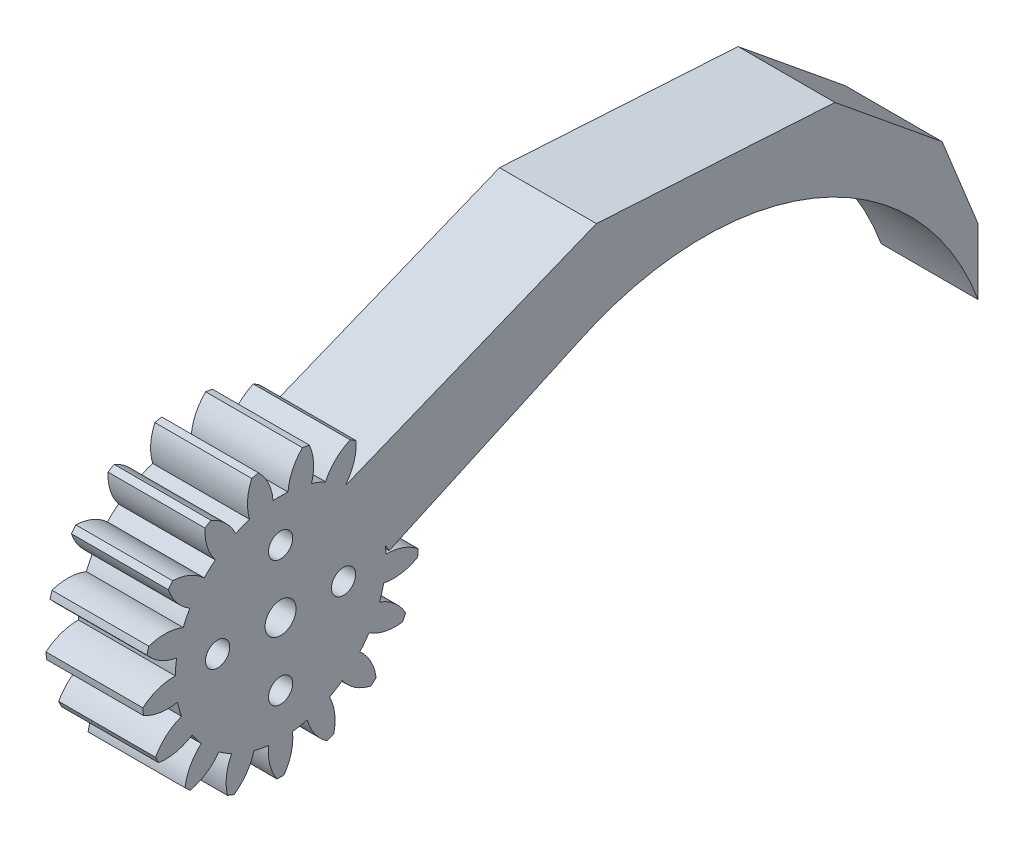
SolidWorks part; units mm, degrees
ref_plane "前视基准面" through (0, 0, 0) normal (0, 0, 1) x (1, 0, 0)
ref_plane "上视基准面" through (0, 0, 0) normal (0, 1, 0) x (1, 0, 0)
ref_plane "右视基准面" through (0, 0, 0) normal (1, 0, 0) x (0, 0, -1)
other "Configuration Table"
sketch "草图1" plane through (0, 0, 0) normal (1, 0, 0) x (0, 0, -1)
  circle A0 centre (-0.6201, 7.5553) radius 12.75 construction
  arc A1 (-14.4217, 11.1021) -> (-11.3496, 9.3222) centre (-10.4888, 14.3491) ccw
  arc A2 (-11.3496, 9.3222) -> (-11.4916, 7.7901) centre (-0.6201, 7.5553) ccw
  arc A3 (-11.4916, 7.7901) -> (-14.8384, 6.605) centre (-11.5692, 2.6907) ccw
  arc A4 (-14.8384, 6.605) -> (-14.7709, 5.8769) centre (-0.6201, 7.5553) ccw
  arc A5 (-14.7709, 5.8769) -> (-11.2633, 5.327) centre (-12.2766, 10.3253) ccw
  arc A6 (-11.2633, 5.327) -> (-10.8423, 3.847) centre (-0.6201, 7.5553) ccw
  arc A7 (-10.8423, 3.847) -> (-13.535, 1.5329) centre (-9.0725, -0.9361) ccw
  arc A8 (-13.535, 1.5329) -> (-13.209, 0.8784) centre (-0.6201, 7.5553) ccw
  arc A9 (-13.209, 0.8784) -> (-9.7397, 1.6327) centre (-12.4901, 5.9274) ccw
  arc A10 (-9.7397, 1.6327) -> (-8.8124, 0.4047) centre (-0.6201, 7.5553) ccw
  arc A11 (-8.8124, 0.4047) -> (-10.4873, -2.7258) centre (-5.4342, -3.416) ccw
  arc A12 (-10.4873, -2.7258) -> (-9.9469, -3.2184) centre (-0.6201, 7.5553) ccw
  arc A13 (-9.9469, -3.2184) -> (-6.9843, -1.2617) centre (-11.1005, 1.7494) ccw
  arc A14 (-6.9843, -1.2617) -> (-5.6761, -2.0718) centre (-0.6201, 7.5553) ccw
  arc A15 (-5.6761, -2.0718) -> (-6.1071, -5.5959) centre (-1.1459, -4.4142) ccw
  arc A16 (-6.1071, -5.5959) -> (-5.4252, -5.8601) centre (-0.6201, 7.5553) ccw
  arc A17 (-5.4252, -5.8601) -> (-3.3695, -2.9654) centre (-8.2954, -1.6444) ccw
  arc A18 (-3.3695, -2.9654) -> (-1.857, -3.2481) centre (-0.6201, 7.5553) ccw
  arc A19 (-1.857, -3.2481) -> (-0.9857, -6.69) centre (3.2135, -3.7958) ccw
  arc A20 (-0.9857, -6.69) -> (-0.2545, -6.69) centre (-0.6201, 7.5553) ccw
  arc A21 (-0.2545, -6.69) -> (0.6167, -3.2481) centre (-4.4538, -3.7958) ccw
  arc A22 (0.6167, -3.2481) -> (2.1292, -2.9654) centre (-0.6201, 7.5553) ccw
  arc A23 (2.1292, -2.9654) -> (4.1849, -5.8601) centre (7.0552, -1.6444) ccw
  arc A24 (4.1849, -5.8601) -> (4.8668, -5.5959) centre (-0.6201, 7.5553) ccw
  arc A25 (4.8668, -5.5959) -> (4.4358, -2.0718) centre (-0.0944, -4.4142) ccw
  arc A26 (4.4358, -2.0718) -> (5.7441, -1.2617) centre (-0.6201, 7.5553) ccw
  arc A27 (5.7441, -1.2617) -> (8.7067, -3.2184) centre (9.8602, 1.7494) ccw
  arc A28 (8.7067, -3.2184) -> (9.2471, -2.7258) centre (-0.6201, 7.5553) ccw
  arc A29 (9.2471, -2.7258) -> (7.5721, 0.4047) centre (4.194, -3.416) ccw
  arc A30 (7.5721, 0.4047) -> (8.4994, 1.6327) centre (-0.6201, 7.5553) ccw
  arc A31 (8.4994, 1.6327) -> (11.9688, 0.8784) centre (11.2498, 5.9274) ccw
  arc A32 (11.9688, 0.8784) -> (12.2947, 1.5329) centre (-0.6201, 7.5553) ccw
  arc A33 (12.2947, 1.5329) -> (9.602, 3.847) centre (7.8322, -0.9361) ccw
  arc A34 (9.602, 3.847) -> (10.0231, 5.327) centre (-0.6201, 7.5553) ccw
  arc A35 (10.0231, 5.327) -> (13.5307, 5.8769) centre (11.0364, 10.3253) ccw
  arc A36 (13.5307, 5.8769) -> (13.5982, 6.605) centre (-0.6201, 7.5553) ccw
  arc A37 (13.5982, 6.605) -> (10.2513, 7.7901) centre (10.3289, 2.6907) ccw
  arc A38 (10.2513, 7.7901) -> (10.1094, 9.3222) centre (-0.6201, 7.5553) ccw
  arc A39 (10.1094, 9.3222) -> (13.1814, 11.1021) centre (9.2486, 14.3491) ccw
  arc A40 (13.1814, 11.1021) -> (12.9813, 11.8054) centre (-0.6201, 7.5553) ccw
  arc A41 (12.9813, 11.8054) -> (9.4324, 11.7014) centre (11.3469, 6.9744) ccw
  arc A42 (9.4324, 11.7014) -> (8.7466, 13.0788) centre (-0.6201, 7.5553) ccw
  arc A43 (8.7466, 13.0788) -> (10.9682, 15.8483) centre (6.128, 17.4553) ccw
  arc A44 (10.9682, 15.8483) -> (10.5275, 16.4318) centre (-0.6201, 7.5553) ccw
  arc A45 (10.5275, 16.4318) -> (7.2558, 15.0529) centre (10.7486, 11.3366) ccw
  arc A46 (7.2558, 15.0529) -> (6.1187, 16.0895) centre (-0.6201, 7.5553) ccw
  arc A47 (6.1187, 16.0895) -> (7.1899, 19.4745) centre (2.0961, 19.2245) ccw
  arc A48 (7.1899, 19.4745) -> (6.5682, 19.8594) centre (-0.6201, 7.5553) ccw
  arc A49 (6.5682, 19.8594) -> (4.0156, 17.3917) centre (8.615, 15.1881) ccw
  arc A50 (4.0156, 17.3917) -> (2.5808, 17.9475) centre (-0.6201, 7.5553) ccw
  arc A51 (2.5808, 17.9475) -> (2.3568, 21.4909) centre (-2.3027, 19.4177) ccw
  arc A52 (2.3568, 21.4909) -> (1.6381, 21.6253) centre (-0.6201, 7.5553) ccw
  arc A53 (1.6381, 21.6253) -> (0.1492, 18.4021) centre (5.234, 18.0088) ccw
  arc A54 (0.1492, 18.4021) -> (-1.3895, 18.4021) centre (-0.6201, 7.5553) ccw
  arc A55 (-1.3895, 18.4021) -> (-2.8783, 21.6253) centre (-6.4743, 18.0088) ccw
  arc A56 (-2.8783, 21.6253) -> (-3.5971, 21.4909) centre (-0.6201, 7.5553) ccw
  arc A57 (-3.5971, 21.4909) -> (-3.821, 17.9475) centre (1.0625, 19.4177) ccw
  arc A58 (-3.821, 17.9475) -> (-5.2558, 17.3917) centre (-0.6201, 7.5553) ccw
  arc A59 (-5.2558, 17.3917) -> (-7.8085, 19.8594) centre (-9.8552, 15.1881) ccw
  arc A60 (-7.8085, 19.8594) -> (-8.4302, 19.4745) centre (-0.6201, 7.5553) ccw
  arc A61 (-8.4302, 19.4745) -> (-7.359, 16.0895) centre (-3.3363, 19.2245) ccw
  arc A62 (-7.359, 16.0895) -> (-8.4961, 15.0529) centre (-0.6201, 7.5553) ccw
  arc A63 (-8.4961, 15.0529) -> (-11.7678, 16.4318) centre (-11.9889, 11.3366) ccw
  arc A64 (-11.7678, 16.4318) -> (-12.2085, 15.8483) centre (-0.6201, 7.5553) ccw
  arc A65 (-12.2085, 15.8483) -> (-9.9868, 13.0788) centre (-7.3683, 17.4553) ccw
  arc A66 (-9.9868, 13.0788) -> (-10.6727, 11.7014) centre (-0.6201, 7.5553) ccw
  arc A67 (-10.6727, 11.7014) -> (-14.2216, 11.8054) centre (-12.5871, 6.9744) ccw
  arc A68 (-14.2216, 11.8054) -> (-14.4217, 11.1021) centre (-0.6201, 7.5553) ccw
extrude "凸台-拉伸1" add sketch "草图1" along normal blind 10
sketch "草图2" plane through (10, 0, 0) normal (1, 0, 0) x (0, 0, -1)
  circle A0 centre (-0.6201, 7.5553) radius 1.7242
  dimension "D1" = 3.4484
extrude "切除-拉伸1" cut sketch "草图2" against normal blind 10
sketch "草图5" [suppressed] plane through (10, 0, 0) normal (1, 0, 0) x (0, 0, -1)
  circle A0 centre (-0.6201, 7.5553) radius 12.75 construction
sketch "草图7" [suppressed] plane through (10, 0, 0) normal (1, 0, 0) x (0, 0, -1)
  line L0 (-38.8515, 60.5868) -> (-49.9964, 49.4419)
  line L1 (-13.0532, 39.26) -> (-111.5146, 39.26) construction
  line L2 (-50.689, 49.4419) -> (-49.9964, 49.4419)
  line L3 (9.7389, 56.4365) -> (20.6157, 52.1796)
  line L4 (-50.689, 49.4419) -> (-90.8971, 49.4419)
  line L5 (-90.8971, 49.4419) -> (-90.8971, 62.9419)
  line L6 (-90.8971, 62.9419) -> (-53.9638, 65.5245)
  line L7 (7.5721, 0.4047) -> (7.5721, 11.8054)
  line L8 (7.5721, 11.8054) -> (44.482, 14.3864)
  line L9 (7.5721, 0.4047) -> (47.7721, 0.4047)
  line L10 (47.7721, 0.4047) -> (58.7323, 11.3649)
  line L11 (107.2323, 7.4047) -> (118.7323, 3.1047)
  arc A0 (-38.8515, 60.5868) -> (9.7389, 56.4365) centre (-17.9459, 18.8274) cw
  arc A1 (-53.9638, 65.5245) -> (20.6157, 52.1796) centre (-22.4221, 26.7287) cw
  arc A2 (58.7323, 11.3649) -> (107.2323, 7.4047) centre (79.7383, -30.3441) cw
  arc A3 (44.482, 14.3864) -> (118.7323, 3.1047) centre (76.6479, -23.8935) cw
  dimension "D5" = 50
  dimension "D12" = 46.7
  dimension "D13" = 46.7
  dimension "D14" = 50
  dimension "D16" = 7
  dimension "D1" = 45
  dimension "D2" = 13.5
  dimension "D3" = 94
  dimension "D4" = 94
  dimension "D6" = 40.2
  dimension "D7" = 37
  dimension "D8" = 135
  dimension "D9" = 15.5
  dimension "D10" = 48.5904
  dimension "D11" = 48.5
  dimension "D15" = 60
  dimension "D17" = 2.7
extrude "凸台-拉伸4" add sketch "草图1<2>" along normal blind 10
sketch "草图1<2>" plane through (0, 0, 0) normal (1, 0, 0) x (0, 0, -1) same geometry as "草图1"
sketch "草图9" plane through (10, 0, 0) normal (1, 0, 0) x (0, 0, -1)
  circle A0 centre (-0.6201, 7.5553) radius 1.6
  dimension "D1" = 3.2
extrude "切除-拉伸2" cut sketch "草图9" against normal blind 10
sketch "草图10" plane through (10, 0, 0) normal (1, 0, 0) x (0, 0, -1)
  circle A0 centre (-0.6201, 7.5553) radius 12.75
  arc A60 (-14.4217, 11.1021) -> (-11.3496, 9.3222) centre (-10.4888, 14.3491) ccw
  arc A61 (-11.3496, 9.3222) -> (-11.4916, 7.7901) centre (-0.6201, 7.5553) ccw
  arc A62 (-11.3496, 9.3222) -> (-11.4916, 7.7901) centre (-0.6201, 7.5553) ccw
  arc A63 (-8.8124, 0.4047) -> (-10.4873, -2.7258) centre (-5.4342, -3.416) ccw
  arc A64 (-10.4873, -2.7258) -> (-9.9469, -3.2184) centre (-0.6201, 7.5553) ccw
  arc A65 (-9.9469, -3.2184) -> (-6.9843, -1.2617) centre (-11.1005, 1.7494) ccw
  arc A66 (-5.6761, -2.0718) -> (-6.1071, -5.5959) centre (-1.1459, -4.4142) ccw
  arc A67 (-6.1071, -5.5959) -> (-5.4252, -5.8601) centre (-0.6201, 7.5553) ccw
  arc A68 (-5.4252, -5.8601) -> (-3.3695, -2.9654) centre (-8.2954, -1.6444) ccw
  arc A69 (-1.857, -3.2481) -> (-0.9857, -6.69) centre (3.2135, -3.7958) ccw
  arc A70 (-0.9857, -6.69) -> (-0.2545, -6.69) centre (-0.6201, 7.5553) ccw
  arc A71 (-0.2545, -6.69) -> (0.6167, -3.2481) centre (-4.4538, -3.7958) ccw
  arc A72 (-11.4916, 7.7901) -> (-14.8384, 6.605) centre (-11.5692, 2.6907) ccw
  arc A73 (0.6167, -3.2481) -> (2.1292, -2.9654) centre (-0.6201, 7.5553) ccw
  arc A74 (2.1292, -2.9654) -> (4.1849, -5.8601) centre (7.0552, -1.6444) ccw
  arc A75 (4.1849, -5.8601) -> (4.8668, -5.5959) centre (-0.6201, 7.5553) ccw
  arc A76 (4.8668, -5.5959) -> (4.4358, -2.0718) centre (-0.0944, -4.4142) ccw
  arc A77 (4.4358, -2.0718) -> (5.7441, -1.2617) centre (-0.6201, 7.5553) ccw
  arc A78 (5.7441, -1.2617) -> (8.7067, -3.2184) centre (9.8602, 1.7494) ccw
  arc A79 (8.7067, -3.2184) -> (9.2471, -2.7258) centre (-0.6201, 7.5553) ccw
  arc A80 (9.2471, -2.7258) -> (7.5721, 0.4047) centre (4.194, -3.416) ccw
  arc A81 (7.5721, 0.4047) -> (8.4994, 1.6327) centre (-0.6201, 7.5553) ccw
  arc A82 (8.4994, 1.6327) -> (11.9688, 0.8784) centre (11.2498, 5.9274) ccw
  arc A83 (11.9688, 0.8784) -> (12.2947, 1.5329) centre (-0.6201, 7.5553) ccw
  arc A84 (12.2947, 1.5329) -> (9.602, 3.847) centre (7.8322, -0.9361) ccw
  arc A85 (9.602, 3.847) -> (10.0231, 5.327) centre (-0.6201, 7.5553) ccw
  arc A86 (10.0231, 5.327) -> (13.5307, 5.8769) centre (11.0364, 10.3253) ccw
  arc A87 (13.5307, 5.8769) -> (13.5982, 6.605) centre (-0.6201, 7.5553) ccw
  arc A88 (13.5982, 6.605) -> (10.2513, 7.7901) centre (10.3289, 2.6907) ccw
  arc A89 (10.2513, 7.7901) -> (10.1094, 9.3222) centre (-0.6201, 7.5553) ccw
  arc A90 (10.1094, 9.3222) -> (13.1814, 11.1021) centre (9.2486, 14.3491) ccw
  arc A91 (13.1814, 11.1021) -> (12.9813, 11.8054) centre (-0.6201, 7.5553) ccw
  arc A92 (12.9813, 11.8054) -> (9.4324, 11.7014) centre (11.3469, 6.9744) ccw
  arc A93 (9.4324, 11.7014) -> (8.7466, 13.0788) centre (-0.6201, 7.5553) ccw
  arc A94 (8.7466, 13.0788) -> (10.9682, 15.8483) centre (6.128, 17.4553) ccw
  arc A95 (10.9682, 15.8483) -> (10.5275, 16.4318) centre (-0.6201, 7.5553) ccw
  arc A96 (10.5275, 16.4318) -> (7.2558, 15.0529) centre (10.7486, 11.3366) ccw
  arc A97 (7.2558, 15.0529) -> (6.1187, 16.0895) centre (-0.6201, 7.5553) ccw
  arc A98 (6.1187, 16.0895) -> (7.1899, 19.4745) centre (2.0961, 19.2245) ccw
  arc A99 (7.1899, 19.4745) -> (6.5682, 19.8594) centre (-0.6201, 7.5553) ccw
  arc A100 (6.5682, 19.8594) -> (4.0156, 17.3917) centre (8.615, 15.1881) ccw
  arc A101 (4.0156, 17.3917) -> (2.5808, 17.9475) centre (-0.6201, 7.5553) ccw
  arc A102 (2.5808, 17.9475) -> (2.3568, 21.4909) centre (-2.3027, 19.4177) ccw
  arc A103 (2.3568, 21.4909) -> (1.6381, 21.6253) centre (-0.6201, 7.5553) ccw
  arc A104 (1.6381, 21.6253) -> (0.1492, 18.4021) centre (5.234, 18.0088) ccw
  arc A105 (0.1492, 18.4021) -> (-1.3895, 18.4021) centre (-0.6201, 7.5553) ccw
  arc A106 (-1.3895, 18.4021) -> (-2.8783, 21.6253) centre (-6.4743, 18.0088) ccw
  arc A107 (-2.8783, 21.6253) -> (-3.5971, 21.4909) centre (-0.6201, 7.5553) ccw
  arc A108 (-3.5971, 21.4909) -> (-3.821, 17.9475) centre (1.0625, 19.4177) ccw
  arc A109 (-3.821, 17.9475) -> (-5.2558, 17.3917) centre (-0.6201, 7.5553) ccw
  arc A110 (-5.2558, 17.3917) -> (-7.8085, 19.8594) centre (-9.8552, 15.1881) ccw
  arc A111 (-7.8085, 19.8594) -> (-8.4302, 19.4745) centre (-0.6201, 7.5553) ccw
  arc A112 (-8.4302, 19.4745) -> (-7.359, 16.0895) centre (-3.3363, 19.2245) ccw
  arc A113 (-7.359, 16.0895) -> (-8.4961, 15.0529) centre (-0.6201, 7.5553) ccw
  arc A114 (-8.4961, 15.0529) -> (-11.7678, 16.4318) centre (-11.9889, 11.3366) ccw
  arc A115 (-11.7678, 16.4318) -> (-12.2085, 15.8483) centre (-0.6201, 7.5553) ccw
  arc A116 (-12.2085, 15.8483) -> (-9.9868, 13.0788) centre (-7.3683, 17.4553) ccw
  arc A117 (-9.9868, 13.0788) -> (-10.6727, 11.7014) centre (-0.6201, 7.5553) ccw
  arc A118 (-10.6727, 11.7014) -> (-14.2216, 11.8054) centre (-12.5871, 6.9744) ccw
  arc A119 (-14.2216, 11.8054) -> (-14.4217, 11.1021) centre (-0.6201, 7.5553) ccw
  arc A120 (-14.4217, 11.1021) -> (-11.3496, 9.3222) centre (-10.4888, 14.3491) ccw
  arc A123 (-8.8124, 0.4047) -> (-10.4873, -2.7258) centre (-5.4342, -3.416) ccw
  arc A124 (-10.4873, -2.7258) -> (-9.9469, -3.2184) centre (-0.6201, 7.5553) ccw
  arc A125 (-9.9469, -3.2184) -> (-6.9843, -1.2617) centre (-11.1005, 1.7494) ccw
  arc A126 (-5.6761, -2.0718) -> (-6.1071, -5.5959) centre (-1.1459, -4.4142) ccw
  arc A127 (-6.1071, -5.5959) -> (-5.4252, -5.8601) centre (-0.6201, 7.5553) ccw
  arc A128 (-5.4252, -5.8601) -> (-3.3695, -2.9654) centre (-8.2954, -1.6444) ccw
  arc A129 (-1.857, -3.2481) -> (-0.9857, -6.69) centre (3.2135, -3.7958) ccw
  arc A130 (-0.9857, -6.69) -> (-0.2545, -6.69) centre (-0.6201, 7.5553) ccw
  arc A131 (-0.2545, -6.69) -> (0.6167, -3.2481) centre (-4.4538, -3.7958) ccw
  arc A133 (0.6167, -3.2481) -> (2.1292, -2.9654) centre (-0.6201, 7.5553) ccw
  arc A134 (2.1292, -2.9654) -> (4.1849, -5.8601) centre (7.0552, -1.6444) ccw
  arc A135 (4.1849, -5.8601) -> (4.8668, -5.5959) centre (-0.6201, 7.5553) ccw
  arc A136 (4.8668, -5.5959) -> (4.4358, -2.0718) centre (-0.0944, -4.4142) ccw
  arc A137 (4.4358, -2.0718) -> (5.7441, -1.2617) centre (-0.6201, 7.5553) ccw
  arc A138 (5.7441, -1.2617) -> (8.7067, -3.2184) centre (9.8602, 1.7494) ccw
  arc A139 (8.7067, -3.2184) -> (9.2471, -2.7258) centre (-0.6201, 7.5553) ccw
  arc A140 (9.2471, -2.7258) -> (7.5721, 0.4047) centre (4.194, -3.416) ccw
  arc A141 (7.5721, 0.4047) -> (8.4994, 1.6327) centre (-0.6201, 7.5553) ccw
  arc A142 (8.4994, 1.6327) -> (11.9688, 0.8784) centre (11.2498, 5.9274) ccw
  arc A143 (11.9688, 0.8784) -> (12.2947, 1.5329) centre (-0.6201, 7.5553) ccw
  arc A144 (12.2947, 1.5329) -> (9.602, 3.847) centre (7.8322, -0.9361) ccw
  arc A145 (9.602, 3.847) -> (10.0231, 5.327) centre (-0.6201, 7.5553) ccw
  arc A146 (10.0231, 5.327) -> (13.5307, 5.8769) centre (11.0364, 10.3253) ccw
  arc A147 (13.5307, 5.8769) -> (13.5982, 6.605) centre (-0.6201, 7.5553) ccw
  arc A148 (13.5982, 6.605) -> (10.2513, 7.7901) centre (10.3289, 2.6907) ccw
  arc A149 (10.2513, 7.7901) -> (10.1094, 9.3222) centre (-0.6201, 7.5553) ccw
  arc A150 (10.1094, 9.3222) -> (13.1814, 11.1021) centre (9.2486, 14.3491) ccw
  arc A151 (13.1814, 11.1021) -> (12.9813, 11.8054) centre (-0.6201, 7.5553) ccw
  arc A152 (12.9813, 11.8054) -> (9.4324, 11.7014) centre (11.3469, 6.9744) ccw
  arc A153 (9.4324, 11.7014) -> (8.7466, 13.0788) centre (-0.6201, 7.5553) ccw
  arc A154 (8.7466, 13.0788) -> (10.9682, 15.8483) centre (6.128, 17.4553) ccw
  arc A155 (10.9682, 15.8483) -> (10.5275, 16.4318) centre (-0.6201, 7.5553) ccw
  arc A156 (10.5275, 16.4318) -> (7.2558, 15.0529) centre (10.7486, 11.3366) ccw
  arc A157 (7.2558, 15.0529) -> (6.1187, 16.0895) centre (-0.6201, 7.5553) ccw
  arc A158 (6.1187, 16.0895) -> (7.1899, 19.4745) centre (2.0961, 19.2245) ccw
  arc A159 (7.1899, 19.4745) -> (6.5682, 19.8594) centre (-0.6201, 7.5553) ccw
  arc A160 (6.5682, 19.8594) -> (4.0156, 17.3917) centre (8.615, 15.1881) ccw
  arc A161 (4.0156, 17.3917) -> (2.5808, 17.9475) centre (-0.6201, 7.5553) ccw
  arc A162 (2.5808, 17.9475) -> (2.3568, 21.4909) centre (-2.3027, 19.4177) ccw
  arc A163 (2.3568, 21.4909) -> (1.6381, 21.6253) centre (-0.6201, 7.5553) ccw
  arc A164 (1.6381, 21.6253) -> (0.1492, 18.4021) centre (5.234, 18.0088) ccw
  arc A165 (0.1492, 18.4021) -> (-1.3895, 18.4021) centre (-0.6201, 7.5553) ccw
  arc A166 (-1.3895, 18.4021) -> (-2.8783, 21.6253) centre (-6.4743, 18.0088) ccw
  arc A167 (-2.8783, 21.6253) -> (-3.5971, 21.4909) centre (-0.6201, 7.5553) ccw
  arc A168 (-3.5971, 21.4909) -> (-3.821, 17.9475) centre (1.0625, 19.4177) ccw
  arc A169 (-3.821, 17.9475) -> (-5.2558, 17.3917) centre (-0.6201, 7.5553) ccw
  arc A170 (-5.2558, 17.3917) -> (-7.8085, 19.8594) centre (-9.8552, 15.1881) ccw
  arc A171 (-7.8085, 19.8594) -> (-8.4302, 19.4745) centre (-0.6201, 7.5553) ccw
  arc A172 (-8.4302, 19.4745) -> (-7.359, 16.0895) centre (-3.3363, 19.2245) ccw
  arc A173 (-7.359, 16.0895) -> (-8.4961, 15.0529) centre (-0.6201, 7.5553) ccw
  arc A174 (-8.4961, 15.0529) -> (-11.7678, 16.4318) centre (-11.9889, 11.3366) ccw
  arc A175 (-11.7678, 16.4318) -> (-12.2085, 15.8483) centre (-0.6201, 7.5553) ccw
  arc A176 (-12.2085, 15.8483) -> (-9.9868, 13.0788) centre (-7.3683, 17.4553) ccw
  arc A177 (-9.9868, 13.0788) -> (-10.6727, 11.7014) centre (-0.6201, 7.5553) ccw
  arc A178 (-10.6727, 11.7014) -> (-14.2216, 11.8054) centre (-12.5871, 6.9744) ccw
  arc A179 (-14.2216, 11.8054) -> (-14.4217, 11.1021) centre (-0.6201, 7.5553) ccw
  arc A189 (-11.4916, 7.7901) -> (-14.8384, 6.605) centre (-11.5692, 2.6907) ccw
  arc A190 (-14.8384, 6.605) -> (-14.7709, 5.8769) centre (-0.6201, 7.5553) ccw
  arc A191 (-14.8384, 6.605) -> (-14.7709, 5.8769) centre (-0.6201, 7.5553) ccw
  arc A192 (-14.7709, 5.8769) -> (-11.2633, 5.327) centre (-12.2766, 10.3253) ccw
  arc A193 (-14.7709, 5.8769) -> (-11.2633, 5.327) centre (-12.2766, 10.3253) ccw
  arc A194 (-11.2633, 5.327) -> (-10.8423, 3.847) centre (-0.6201, 7.5553) ccw
  arc A195 (-11.2633, 5.327) -> (-10.8423, 3.847) centre (-0.6201, 7.5553) ccw
  arc A196 (-10.8423, 3.847) -> (-13.535, 1.5329) centre (-9.0725, -0.9361) ccw
  arc A197 (-10.8423, 3.847) -> (-13.535, 1.5329) centre (-9.0725, -0.9361) ccw
  arc A198 (-13.535, 1.5329) -> (-13.209, 0.8784) centre (-0.6201, 7.5553) ccw
  arc A199 (-13.535, 1.5329) -> (-13.209, 0.8784) centre (-0.6201, 7.5553) ccw
  arc A200 (-13.209, 0.8784) -> (-9.7397, 1.6327) centre (-12.4901, 5.9274) ccw
  arc A201 (-13.209, 0.8784) -> (-9.7397, 1.6327) centre (-12.4901, 5.9274) ccw
  arc A202 (-9.7397, 1.6327) -> (-8.8124, 0.4047) centre (-0.6201, 7.5553) ccw
  arc A203 (-9.7397, 1.6327) -> (-8.8124, 0.4047) centre (-0.6201, 7.5553) ccw
  arc A204 (-6.9843, -1.2617) -> (-5.6761, -2.0718) centre (-0.6201, 7.5553) ccw
  arc A205 (-6.9843, -1.2617) -> (-5.6761, -2.0718) centre (-0.6201, 7.5553) ccw
  arc A206 (-3.3695, -2.9654) -> (-1.857, -3.2481) centre (-0.6201, 7.5553) ccw
  arc A207 (-3.3695, -2.9654) -> (-1.857, -3.2481) centre (-0.6201, 7.5553) ccw
  dimension "D1" = 0
sketch "草图11" plane through (10, 0, 0) normal (1, 0, 0) x (0, 0, -1)
  circle A0 centre (-0.6201, 7.5553) radius 6.5 construction
  circle A1 centre (-0.6201, 14.0553) radius 1.25
  circle A2 centre (5.8799, 7.5553) radius 1.25
  circle A3 centre (-0.6201, 1.0553) radius 1.25
  circle A4 centre (-7.1201, 7.5553) radius 1.25
  point P14 (-0.6201, 7.5553)
  dimension "D1" = 13
  dimension "D2" = 2.5
  dimension "D3" = 4
extrude "切除-拉伸3" cut sketch "草图11" against normal blind 10
sketch "草图16" plane through (0, 0, 0) normal (-1, 0, 0) x (0, 0, 1)
  line L7 (-10.5838, 7.9332) -> (-29.994, 16.7814)
  line L8 (-6.0229, 16.0052) -> (-31.9882, 26.4872)
  line L9 (-31.9882, 26.4872) -> (-56.6165, 25.0016)
  line L10 (-56.6165, 25.0016) -> (-67.6736, 15.9769)
  line L11 (-67.6736, 15.9769) -> (-71.3852, 6.7826)
  line L12 (-71.3852, 6.7826) -> (-71.3852, -0.0021)
  line L13 (-6.0229, 16.0052) -> (-10.5838, 7.9332)
  arc A1 (-29.994, 16.7814) -> (-71.3852, -0.0021) centre (-43.0677, -10.4074) ccw
extrude "凸台-拉伸6" add sketch "草图16" against normal blind 10
